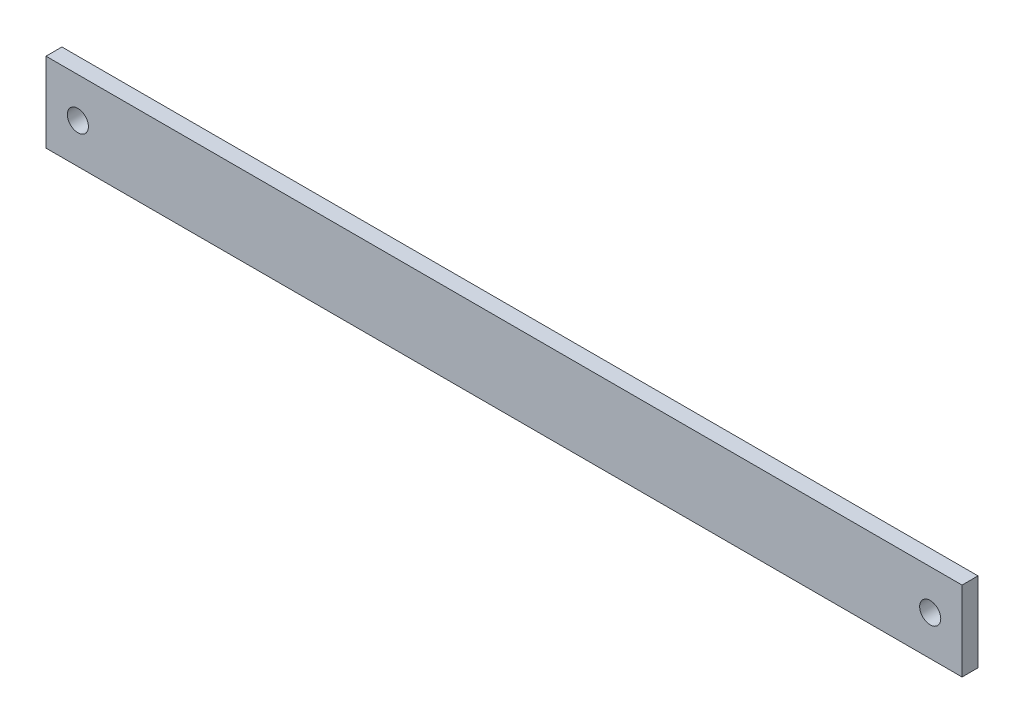
SolidWorks part; units mm, degrees
ref_plane "Front Plane" through (0, 0, 0) normal (0, 0, 1) x (1, 0, 0)
ref_plane "Top Plane" through (0, 0, 0) normal (0, 1, 0) x (1, 0, 0)
ref_plane "Right Plane" through (0, 0, 0) normal (1, 0, 0) x (0, 0, -1)
sketch "Extrusion Base Sketch" plane through (0, 0, 0) normal (0, 0, 1) x (1, 0, 0)
  line L0 (208.75, 17.5) -> (208.75, -2.5)
  line L1 (0, 0) -> (187.5, 0) construction
  line L2 (0, 0) -> (0, 15) construction
  line L3 (0, 15) -> (187.5, 15) construction
  line L4 (187.5, 0) -> (187.5, 15) construction
  line L5 (-21.25, 17.5) -> (208.75, 17.5)
  line L6 (-2.5, 17.5) -> (-2.5, -2.5) construction
  line L7 (-21.25, -2.5) -> (208.75, -2.5)
  line L8 (190, 17.5) -> (190, -2.5) construction
  line L9 (-21.25, 17.5) -> (-21.25, -2.5)
  line L11 (200.75, 7.5) -> (208.75, 7.5) construction
  circle A0 centre (-13.25, 7.5) radius 2.65
  circle A2 centre (200.75, 7.5) radius 2.65
  dimension "D8" = 5.3
  dimension "D1" = 15
  dimension "D2" = 187.5
  dimension "D4" = 2.5
  dimension "D5" = 2.5
  dimension "D6" = 2.5
  dimension "D3" = 20
extrude "Extrusion Base Extrude" add sketch "Extrusion Base Sketch" against normal blind 4
equation "\"Logo Height\"= 15mm"
equation "\"Total Height\"= 20mm"
equation "\"Border\"= ( \"Total Height\" - \"Logo Height\" ) / 2"
equation "\"Text Length\"= 187.5mm"
equation "\"D1@Extrusion Base Sketch\" = \"Logo Height\""
equation "\"D2@Extrusion Base Sketch\" = \"Text Length\""
equation "\"D4@Extrusion Base Sketch\" = \"Border\""
equation "\"D5@Extrusion Base Sketch\" = \"Border\""
equation "\"D6@Extrusion Base Sketch\" = \"Border\""
equation "\"D3@Extrusion Base Sketch\" = \"Total Height\""
